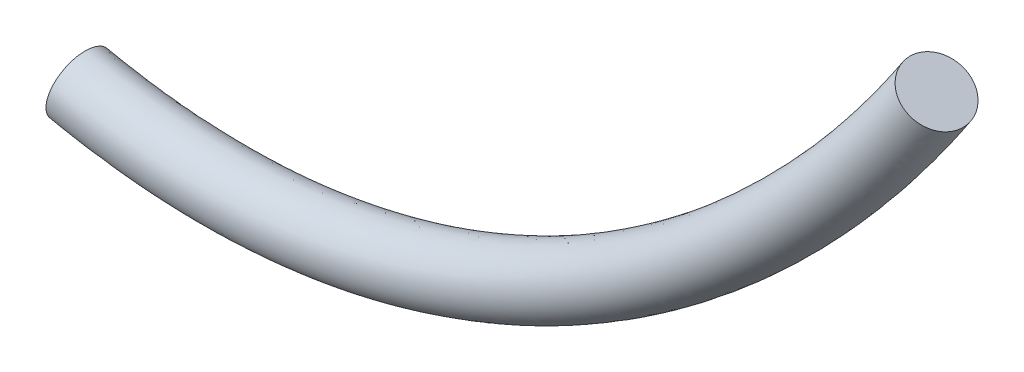
SolidWorks part; units mm, degrees
material "201 軟ｽﾃﾝﾚｽ鋼 (SS)"
ref_plane "正面" through (0, 0, 0) normal (0, 0, 1) x (1, 0, 0)
ref_plane "平面" through (0, 0, 0) normal (0, 1, 0) x (1, 0, 0)
ref_plane "右側面" through (0, 0, 0) normal (1, 0, 0) x (0, 0, -1)
sketch "ｽｹｯﾁ1" plane through (0, 0, 0) normal (0, 0, 1) x (1, 0, 0)
  spline S0 degree 3 poles (0, 0) (456.8642, -96.753) (845.7281, 180.4836) (1077.0242, 529.1681) knots 0 0 0 0 1 1 1 1
  dimension "D1" = 1200
sweep "ｽｲｰﾌﾟ1" add path "ｽｹｯﾁ1" circular profile diameter 80 parameters "D3"=80
